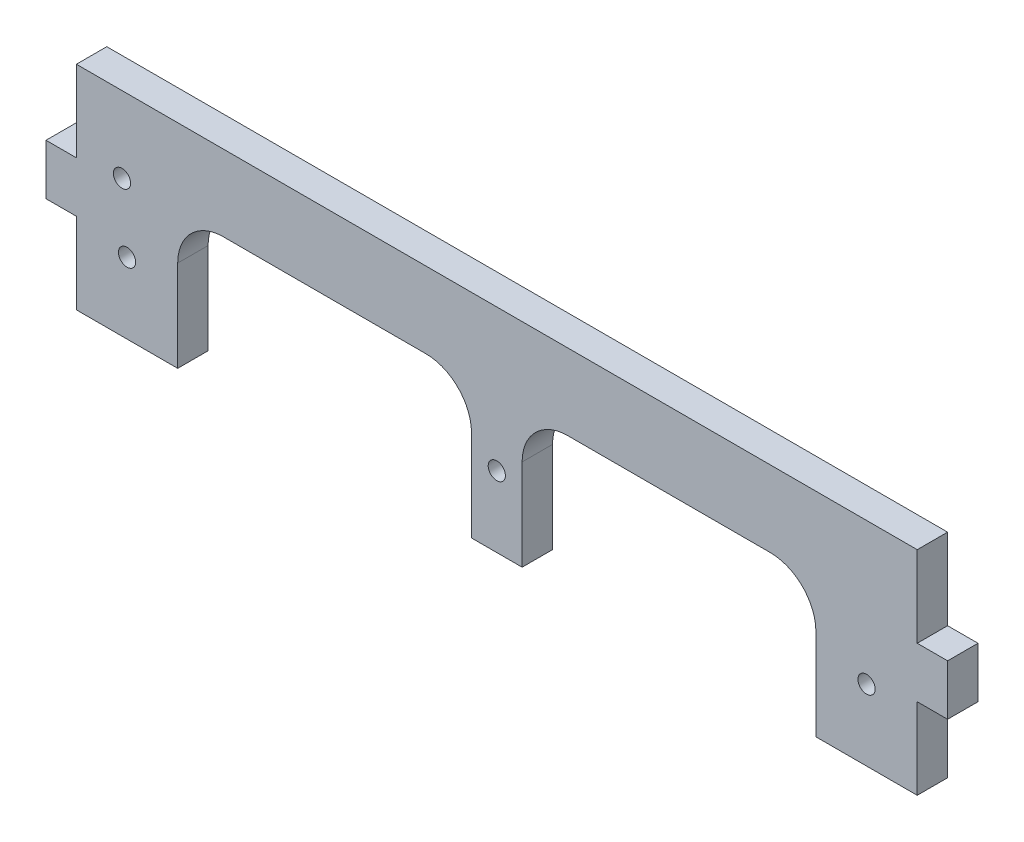
SolidWorks part; units mm, degrees
ref_plane "Front Plane" through (0, 0, 0) normal (0, 0, 1) x (1, 0, 0)
ref_plane "Top Plane" through (0, 0, 0) normal (0, 1, 0) x (1, 0, 0)
ref_plane "Right Plane" through (0, 0, 0) normal (1, 0, 0) x (0, 0, -1)
sketch "Sketch1" plane through (0, 0, 0) normal (0, 0, 1) x (1, 0, 0)
  line L0 (0, 0) -> (0, 16)
  line L1 (0, 42) -> (166, 42)
  line L2 (166, 42) -> (166, 26)
  line L3 (166, 0) -> (146, 0)
  line L4 (146, 0) -> (146, 27)
  line L5 (146, 27) -> (88, 27)
  line L6 (88, 27) -> (88, 0)
  line L7 (88, 0) -> (78, 0)
  line L8 (78, 0) -> (78, 27)
  line L9 (78, 27) -> (20, 27)
  line L10 (20, 27) -> (20, 0)
  line L11 (20, 0) -> (0, 0)
  line L12 (0, 26) -> (-6, 26)
  line L13 (-6, 26) -> (-6, 16)
  line L14 (-6, 16) -> (0, 16)
  line L15 (0, 26) -> (0, 42)
  line L16 (83, 42) -> (83, 0) construction
  line L17 (83, 21) -> (0, 21) construction
  line L18 (-6, 21) -> (20, 21) construction
  line L19 (172, 16) -> (166, 16)
  line L20 (172, 26) -> (172, 16)
  line L21 (166, 26) -> (172, 26)
  line L22 (166, 16) -> (166, 0)
  point P23 (0, 0)
  dimension "D1" = 27
  dimension "D2" = 10
  dimension "D3" = 58
  dimension "D4" = 20
  dimension "D5" = 15
  dimension "D6" = 20
  dimension "D7" = 10
  dimension "D8" = 6
extrude "Boss-Extrude1" add sketch "Sketch1" along normal blind 6
fillet "Fillet1" radius 9 4 edges at (146, 27, 3) (88, 27, 3) (78, 27, 3) (20, 27, 3)
fillet "Fillet2" [suppressed] radius 9
sketch "Sketch2" plane through (0, 0, 6) normal (0, 0, 1) x (1, 0, 0)
  line L0 (83, 42) -> (83, 0) construction
  line L1 (166, 42) -> (0, 42) construction
  line L2 (78, 0) -> (88, 0) construction
  line L3 (10, 0) -> (10, 42) construction
  line L4 (0, 0) -> (20, 0) construction
  line L5 (156, 0) -> (156, 42) construction
  line L6 (146, 0) -> (166, 0) construction
  line L7 (10, 14) -> (162.8081, 14) construction
  circle A0 centre (10, 14) radius 1.7
  circle A1 centre (83, 14) radius 1.7
  circle A2 centre (156, 14) radius 1.7
  point P20 (0, 0)
  point P22 (83, 15.5)
  point P23 (156, 15.5)
  dimension "D1" = 3.4
  dimension "D5" = 3.4
  dimension "D6" = 3.4
  dimension "D4" = 14
extrude "Cut-Extrude1" cut sketch "Sketch2" against normal through all
sketch "Sketch3" plane through (0, 0, 6) normal (0, 0, 1) x (1, 0, 0)
  circle A0 centre (9, 27) radius 1.7
  dimension "D1" = 3.4
extrude "Cut-Extrude2" cut sketch "Sketch3" against normal through all
